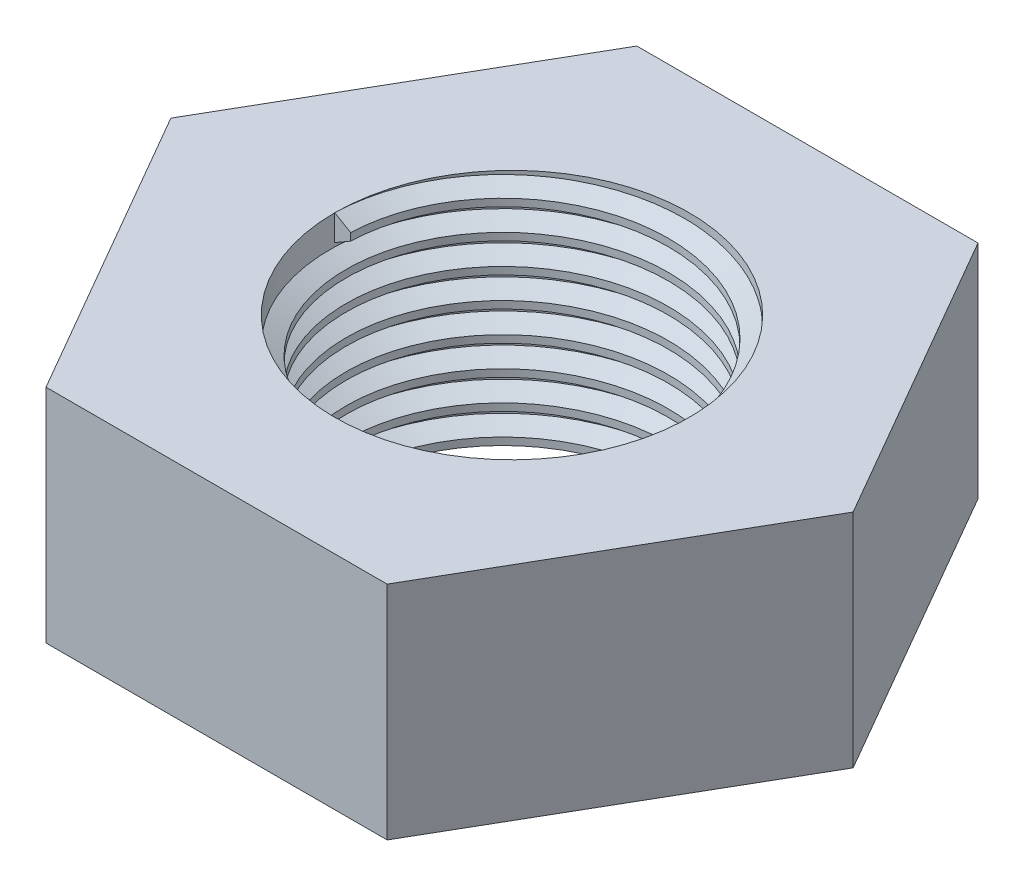
SolidWorks part; units mm, degrees
ref_plane "Front Plane" through (0, 0, 0) normal (0, 0, 1) x (1, 0, 0)
ref_plane "Top Plane" through (0, 0, 0) normal (0, 1, 0) x (1, 0, 0)
ref_plane "Right Plane" through (0, 0, 0) normal (1, 0, 0) x (0, 0, -1)
sketch "Sketch2" plane through (0, 0, 0) normal (0, 1, 0) x (1, 0, 0)
  line L1 (23.094, 0) -> (11.547, 20)
  line L2 (11.547, 20) -> (-11.547, 20)
  line L3 (-11.547, 20) -> (-23.094, 0)
  line L4 (-23.094, 0) -> (-11.547, -20)
  line L5 (-11.547, -20) -> (11.547, -20)
  line L6 (11.547, -20) -> (23.094, 0)
  circle A0 centre (0, 0) radius 20 construction
extrude "Boss-Extrude1" add sketch "Sketch2" along normal blind 15
sketch "Sketch3" plane through (0, 15, 0) normal (0, 1, 0) x (1, 0, 0)
  circle A0 centre (0, 0) radius 12
  dimension "D1" = 24
extrude "Cut-Extrude1" cut sketch "Sketch3" against normal through all
thread "Thread3" pitch 2 method extrude profile "Thread Profile3" start angle 0, offset 0, length 15, pitch 2, diameter 24
ref_plane "Plane3" through (-12, 15, 0) normal (0, 0, 1) x (-1, 0, 0)
sketch "Thread Profile3" plane through (-12, 15, 0) normal (0, 0, 1) x (-1, 0, 0)
  line L0 (0, 0) -> (0, 2) construction
  line L11 (0, 0) -> (0, 1.75)
  line L12 (0, 1.75) -> (-1.0825, 1.125)
  line L13 (-1.0825, 1.125) -> (-1.0825, 0.625)
  line L15 (-1.0825, 0.625) -> (0, 0)
  line L17 (-1.0825, 0.875) -> (0, 0.875) construction
  point P2 (0, 0)
  dimension "Pitch" = 2
  dimension "Profile_Angle" = 60
  dimension "Profile_Land" = 0.5
  dimension "Profile_Height" = 1.0825
